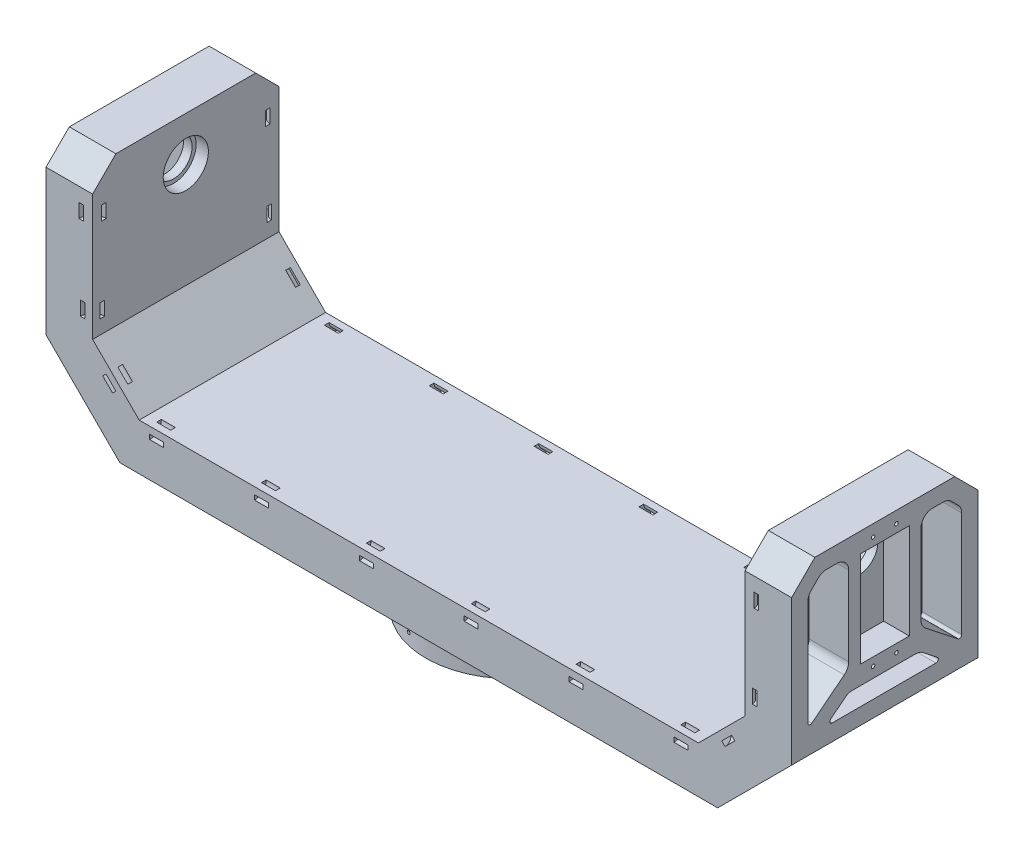
SolidWorks part; units mm, degrees
material "ПК/АБС"
ref_plane "Спереди" through (0, 0, 0) normal (0, 0, 1) x (1, 0, 0)
ref_plane "Сверху" through (0, 0, 0) normal (0, 1, 0) x (1, 0, 0)
ref_plane "Справа" through (0, 0, 0) normal (1, 0, 0) x (0, 0, -1)
sketch "Эскиз1" plane through (0, 0, 0) normal (0, 0, 1) x (1, 0, 0)
  line L0 (0, 0) -> (120, 0)
  line L1 (120, 0) -> (140, 20)
  line L2 (140, 20) -> (140, 84)
  line L3 (140, 84) -> (160, 84)
  line L4 (160, 84) -> (160, 11.7157)
  line L5 (160, 11.7157) -> (128.2843, -20)
  line L6 (128.2843, -20) -> (0, -20)
  line L7 (84.5164, 65) -> (381.3693, 65) construction
  line L8 (0, -20) -> (0, 0)
  dimension "D1" = 65
  dimension "D2" = 20
  dimension "D3" = 20
  dimension "D4" = 20
  dimension "D5" = 140
  dimension "D6" = 19
  dimension "D7" = 120
extrude "Бобышка-Вытянуть1" add sketch "Эскиз1" along normal blind 40 and the other way blind 40
mirror "Зеркальное отражение1" about plane through (0, 0, 0) normal (1, 0, 0) of "Бобышка-Вытянуть1"
chamfer "Фаска1" distance 10 angle 45 4 edges at (150, 84, 40) (150, 84, -40) (-150, 84, -40) (-150, 84, 40)
sketch "Эскиз2" plane through (0, 0, 0) normal (0, 0, 1) x (1, 0, 0)
  line L0 (49.8547, 65) -> (209.3236, 65) construction
  line L1 (120, 0) -> (-120, 0) construction
  line L2 (140, 74.7) -> (145.2775, 74.7)
  line L3 (140, 74) -> (140, 20) construction
  line L4 (145.2775, 74.7) -> (145.2775, 73)
  line L5 (145.2775, 73) -> (160, 73)
  line L6 (160, 11.7157) -> (160, 74) construction
  line L7 (160, 73) -> (160, 65)
  line L8 (160, 65) -> (140, 65)
  line L9 (140, 65) -> (140, 74.7)
  dimension "D1" = 65
  dimension "D2" = 9.7
  dimension "D3" = 8
revolve "Вырез-Повернуть1" cut sketch "Эскиз2" angle 360 about L0
mirror "Зеркальное отражение2" about plane through (0, 0, 0) normal (1, 0, 0) of "Вырез-Повернуть1"
sketch "Эскиз3" plane through (-160, 0, 0) normal (-1, 0, 0) x (0, 0, 1)
  line L0 (-5, 79) -> (-5, 31) construction
  line L1 (-5, 31) -> (5, 31) construction
  line L2 (5, 31) -> (5, 79) construction
  line L3 (5, 79) -> (-5, 79) construction
  line L4 (0, 65) -> (-11.5647, 65) construction
  line L5 (0, 65) -> (0, 85.8977) construction
  circle A0 centre (-5, 79) radius 0.75
  circle A1 centre (5, 79) radius 0.75
  circle A2 centre (-5, 31) radius 0.75
  circle A3 centre (5, 31) radius 0.75
  dimension "D1" = 14
  dimension "D2" = 34
  dimension "D3" = 5
  dimension "D4" = 5
extrude "Вырез-Вытянуть1" cut sketch "Эскиз3" against normal blind 10
sketch "Эскиз4" plane through (-160, 0, 0) normal (-1, 0, 0) x (0, 0, 1)
  line L0 (10.5, 75.5) -> (-10.5, 75.5)
  line L2 (-10.5, 75.5) -> (-10.5, 34.5)
  line L3 (10.5, 34.5) -> (-10.5, 34.5)
  line L5 (0, 65) -> (0, 45.2847) construction
  line L6 (10.5, 75.5) -> (10.5, 34.5)
  dimension "D1" = 10.5
  dimension "D2" = 10.5
  dimension "D3" = 21
  dimension "D4" = 30.5
extrude "Вырез-Вытянуть2" cut sketch "Эскиз4" against normal blind 11
sketch "Эскиз7" plane through (0, -20, 0) normal (0, -1, 0) x (1, 0, 0)
  line L8 (-30, 10.5) -> (10, 10.5)
  line L10 (-30, -10.5) -> (10, -10.5)
  line L12 (-30.5, -10) -> (-30.5, 10)
  line L13 (10.5, -10) -> (10.5, 10)
  line L16 (120.2843, -32) -> (120.2843, 32)
  line L17 (120.2843, 32) -> (-120.2843, 32)
  line L18 (-120.2843, 32) -> (-120.2843, -32)
  line L19 (-120.2843, -32) -> (120.2843, -32)
  line L20 (120.2843, -32) -> (120.2843, 32)
  line L21 (120.2843, 32) -> (-120.2843, 32)
  line L22 (-120.2843, 32) -> (-120.2843, -32)
  line L23 (-120.2843, -32) -> (120.2843, -32)
  circle A0 centre (0, 0) radius 40 construction
  arc A9 (10, 10.5) -> (10.5, 10) centre (10, 10) cw
  arc A10 (10.5, -10) -> (10, -10.5) centre (10, -10) cw
  arc A11 (-30, -10.5) -> (-30.5, -10) centre (-30, -10) cw
  arc A12 (-30.5, 10) -> (-30, 10.5) centre (-30, 10) cw
  dimension "D1" = 8
  dimension "D4" = 0.5
sketch "Эскиз8" plane through (0, -20, 0) normal (0, -1, 0) x (1, 0, 0)
  circle A0 centre (0, 0) radius 37
  circle A1 centre (0, 0) radius 33
  dimension "D1" = 66
  dimension "D2" = 74
extrude "Бобышка-Вытянуть2" add sketch "Эскиз8" along normal blind 10
extrude "Вырез-Вытянуть4" cut sketch "Эскиз7" against normal blind 18.5 contours A12 L12 A11 L10 A10 L13 A9 L8 region at (-10, -20, 0)
sketch "Эскиз9" plane through (0, -20, 0) normal (0, -1, 0) x (1, 0, 0)
  line L0 (-31.5, 10) -> (-31.5, -10)
  line L1 (11.5, 10) -> (11.5, -10)
  line L2 (-38.5, 10) -> (-38.5, -10)
  line L3 (18.5, 10) -> (18.5, -10)
  line L4 (-38.5, 10) -> (-31.5, 10)
  line L5 (-38.5, -10) -> (-31.5, -10)
  line L6 (11.5, 10) -> (18.5, 10)
  line L7 (18.5, -10) -> (11.5, -10)
  dimension "D1" = 7
  dimension "D2" = 7
extrude "Бобышка-Вытянуть3" add sketch "Эскиз9" along normal blind 6
sketch "Эскиз10" plane through (0, -26, 0) normal (0, -1, 0) x (1, 0, 0)
  line L0 (-38.5, 10) -> (-30.5, 10)
  line L1 (-35.623, 10) -> (-38.5, 10) construction
  line L2 (-30.5, 10) -> (-30.5, -10)
  line L3 (-30.5, -10) -> (-38.5, -10)
  line L4 (-38.5, -10) -> (-38.5, 10)
  dimension "D1" = 8
extrude "Вырез-Вытянуть5" cut sketch "Эскиз10" along normal blind 10.5
ref_plane "Плоскость1" through (40, 0, 0) normal (1, 0, 0) x (0, 0, -1)
sketch "Эскиз11" plane through (40, 0, 0) normal (1, 0, 0) x (0, 0, -1)
  line L0 (0, 27.9927) -> (0, -39.0549) construction
  line L1 (-37, -25) -> (45.8184, -25) construction
  line L2 (-37, -20) -> (-37, -30) construction
  circle A0 centre (0, -25) radius 0.75
extrude "Вырез-Вытянуть6" cut sketch "Эскиз11" against normal blind 10.5
pattern_circular "Круговой массив1" count 7 over 360 about axis through (0, -30, 0) along (0, 1, 0) of "Вырез-Вытянуть6"
mirror "Зеркальное отражение3" about plane through (0, 0, 0) normal (1, 0, 0) of "Вырез-Вытянуть2", "Вырез-Вытянуть1"
sketch "Эскиз12" plane through (-160, 0, 0) normal (-1, 0, 0) x (0, 0, 1)
  line L0 (-31.5355, 72.565) -> (-28.565, 75.5355)
  line L1 (-25.0294, 77) -> (-20.5, 77)
  line L2 (-15.5, 72) -> (-15.5, 37.9357)
  line L3 (22.6012, 18.7157) -> (-21.9677, 18.7157)
  line L4 (-33, 23.763) -> (-33, 69.0294)
  line L5 (-40, 11.7157) -> (-40, 74) construction
  line L6 (-30, 84) -> (-40, 74) construction
  line L7 (-30, 84) -> (30, 84) construction
  line L8 (-10.5, 75.5) -> (-10.5, 34.5) construction
  line L9 (-40, 11.7157) -> (40, 11.7157) construction
  line L10 (0, 14.9515) -> (0, 96.0937) construction
  line L11 (33, 23.763) -> (33, 69.0294)
  line L13 (15.5, 72) -> (15.5, 37.9357)
  line L14 (25.0294, 77) -> (20.5, 77)
  line L15 (31.5355, 72.565) -> (28.565, 75.5355)
  line L18 (-22.5873, 20.5007) -> (-16.3487, 25.4248)
  line L19 (16.9822, 25.4248) -> (23.2207, 20.5007)
  line L20 (-31.3804, 22.978) -> (-17.4022, 34.011)
  line L21 (17.4022, 34.011) -> (31.3804, 22.978)
  line L22 (-13.2509, 26.5) -> (13.8844, 26.5)
  line L23 (-10.5, 34.5) -> (10.5, 34.5) construction
  arc A0 (-33, 69.0294) -> (-31.5355, 72.565) centre (-28, 69.0294) cw
  arc A1 (-28.565, 75.5355) -> (-25.0294, 77) centre (-25.0294, 72) cw
  arc A2 (-15.5, 72) -> (-20.5, 77) centre (-20.5, 72) ccw
  arc A7 (15.5, 72) -> (20.5, 77) centre (20.5, 72) cw
  arc A8 (28.565, 75.5355) -> (25.0294, 77) centre (25.0294, 72) ccw
  arc A9 (33, 69.0294) -> (31.5355, 72.565) centre (28, 69.0294) ccw
  arc A10 (23.2207, 20.5007) -> (22.6012, 18.7157) centre (22.6012, 19.7157) cw
  arc A11 (-22.5873, 20.5007) -> (-21.9677, 18.7157) centre (-21.9677, 19.7157) ccw
  arc A12 (16.9822, 25.4248) -> (13.8844, 26.5) centre (13.8844, 21.5) ccw
  arc A13 (-13.2509, 26.5) -> (-16.3487, 25.4248) centre (-13.2509, 21.5) ccw
  arc A14 (33, 23.763) -> (31.3804, 22.978) centre (32, 23.763) cw
  arc A15 (-31.3804, 22.978) -> (-33, 23.763) centre (-32, 23.763) cw
  arc A16 (17.4022, 34.011) -> (15.5, 37.9357) centre (20.5, 37.9357) cw
  arc A17 (-15.5, 37.9357) -> (-17.4022, 34.011) centre (-20.5, 37.9357) cw
  point P53 (-37.8315, 8.9684)
  point P54 (-8.3315, 32.2527)
  point P55 (8.3315, 32.2527)
  point P56 (37.8315, 8.9684)
  point P57 (-42.1685, 14.4631)
  point P58 (-12.6685, 37.7473)
  point P59 (12.6685, 37.7473)
  point P60 (42.1685, 14.4631)
  dimension "D6" = 5
  dimension "D7" = 1
  dimension "D8" = 1
  dimension "D10" = 5
  dimension "D11" = 1
  dimension "D12" = 1
  dimension "D13" = 5
  dimension "D1" = 7
  dimension "D2" = 7
  dimension "D3" = 7
  dimension "D4" = 5
  dimension "D5" = 7
  dimension "D9" = 8
extrude "Вырез-Вытянуть7" cut sketch "Эскиз12" against normal blind 17
sketch "Эскиз13" plane through (-74.1421, -74.1421, 0) normal (-0.7071, -0.7071, 0) x (0, 0, 1)
  line L6 (-16.5294, 114.4214) -> (16.5294, 114.4214)
  line L7 (17.0185, 112.5491) -> (1.4671, 103.8301)
  line L8 (-40, 121.4214) -> (40, 121.4214) construction
  line L10 (1.4671, 94.1598) -> (17.0185, 85.4408)
  line L11 (8.7126, 98.1227) -> (31.511, 85.3406)
  line L12 (-31.511, 112.6493) -> (-8.7126, 99.8672)
  line L13 (31.511, 112.6493) -> (8.7126, 99.8672)
  line L14 (-17.0185, 112.5491) -> (-1.4671, 103.8301)
  line L15 (-16.5294, 83.5685) -> (16.5294, 83.5685)
  line L16 (-1.4671, 94.1598) -> (-17.0185, 85.4408)
  line L17 (-8.7126, 98.1227) -> (-31.511, 85.3406)
  line L18 (-33, 111.7771) -> (-33, 86.2128)
  line L19 (-40, 76.5685) -> (40, 76.5685) construction
  line L22 (33, 111.7771) -> (33, 86.2128)
  line L24 (-40, 76.5685) -> (-40, 121.4214) construction
  line L25 (40, 76.5685) -> (40, 121.4214) construction
  arc A0 (-1.4671, 94.1598) -> (1.4671, 94.1598) centre (0, 91.543) cw
  arc A1 (1.4671, 103.8301) -> (-1.4671, 103.8301) centre (0, 106.4469) cw
  arc A4 (31.511, 85.3406) -> (33, 86.2128) centre (32, 86.2128) ccw
  arc A5 (33, 111.7771) -> (31.511, 112.6493) centre (32, 111.7771) ccw
  arc A6 (-31.511, 112.6493) -> (-33, 111.7771) centre (-32, 111.7771) ccw
  arc A7 (-33, 86.2128) -> (-31.511, 85.3406) centre (-32, 86.2128) ccw
  arc A12 (8.7126, 98.1227) -> (8.7126, 99.8672) centre (9.2017, 98.9949) cw
  arc A13 (-8.7126, 98.1227) -> (-8.7126, 99.8672) centre (-9.2017, 98.9949) ccw
  arc A14 (-16.5294, 83.5685) -> (-17.0185, 85.4408) centre (-16.5294, 84.5685) cw
  arc A15 (16.5294, 83.5685) -> (17.0185, 85.4408) centre (16.5294, 84.5685) ccw
  arc A16 (17.0185, 112.5491) -> (16.5294, 114.4214) centre (16.5294, 113.4214) ccw
  arc A17 (-17.0185, 112.5491) -> (-16.5294, 114.4214) centre (-16.5294, 113.4214) cw
  point P20 (0, 94.9824)
  point P29 (-7.1569, 98.9949)
  dimension "D2" = 3
  dimension "D1" = 1
  dimension "D5" = 1
  dimension "D3" = 7
  dimension "D4" = 7
  dimension "D6" = 7
  dimension "D7" = 7
extrude "Вырез-Вытянуть8" cut sketch "Эскиз13" against normal blind 15
sketch "Эскиз14" plane through (0, -20, 0) normal (0, -1, 0) x (1, 0, 0)
  line L0 (-59.773, 1.6912) -> (-37.4271, 15.7975)
  line L1 (73.5087, -33) -> (107.8127, -33)
  line L2 (-78.2445, 1.6912) -> (-118.2167, 26.9245)
  line L3 (-63.4411, 7.6537) -> (-29.1372, 29.3088)
  line L5 (30.2048, -33) -> (64.5087, -33)
  line L6 (121.2843, -25.2333) -> (121.2843, 25.2333)
  line L7 (107.8127, 33) -> (73.5087, 33)
  line L8 (0, 0) -> (0, -74.0699) construction
  line L9 (-74.5763, 7.6537) -> (-108.8803, 29.3088)
  line L10 (-37.4271, -15.7975) -> (-59.773, -1.6912)
  line L11 (-108.8803, -29.3088) -> (-74.5763, -7.6537)
  line L12 (118.2167, -26.9245) -> (78.2445, -1.6912)
  line L13 (29.1372, -29.3088) -> (63.4411, -7.6537)
  line L14 (108.8803, -29.3088) -> (74.5763, -7.6537)
  line L15 (37.4271, -15.7975) -> (59.773, -1.6912)
  line L16 (74.5763, 7.6537) -> (108.8803, 29.3088)
  line L17 (-29.1372, -29.3088) -> (-63.4411, -7.6537)
  line L18 (-118.2167, -26.9245) -> (-78.2445, -1.6912)
  line L19 (-107.8127, 33) -> (-73.5087, 33)
  line L20 (-121.2843, -25.2333) -> (-121.2843, 25.2333)
  line L21 (-30.2048, -33) -> (-64.5087, -33)
  line L22 (63.4411, 7.6537) -> (29.1372, 29.3088)
  line L23 (78.2445, 1.6912) -> (118.2167, 26.9245)
  line L24 (59.773, 1.6912) -> (37.4271, 15.7975)
  line L25 (-35.623, -10) -> (-38.5, -10)
  line L26 (-38.5, -10) -> (-38.5, 10)
  line L27 (-38.5, 10) -> (-35.623, 10)
  line L28 (66.5087, -9.3449) -> (66.5087, -31)
  line L29 (-71.5087, 31) -> (-71.5087, 9.3449)
  line L30 (-66.5087, 31) -> (-66.5087, 9.3449)
  line L31 (-71.5087, -9.3449) -> (-71.5087, -31)
  line L32 (-66.5087, -9.3449) -> (-66.5087, -31)
  line L33 (71.5087, -9.3449) -> (71.5087, -31)
  line L34 (66.5087, 31) -> (66.5087, 9.3449)
  line L35 (71.5087, 31) -> (71.5087, 9.3449)
  line L36 (-73.5087, -33) -> (-107.8127, -33)
  line L37 (-64.5087, 33) -> (-30.2048, 33)
  line L38 (64.5087, 33) -> (30.2048, 33)
  arc A1 (30.2048, -33) -> (29.1372, -29.3088) centre (30.2048, -31) cw
  arc A2 (34.4949, -13.3829) -> (34.4949, 13.3829) centre (0, 0) ccw
  arc A4 (34.4949, -13.3829) -> (37.4271, -15.7975) centre (36.3595, -14.1063) ccw
  arc A5 (59.773, -1.6912) -> (59.773, 1.6912) centre (58.7054, 0) ccw
  arc A6 (34.4949, 13.3829) -> (37.4271, 15.7975) centre (36.3595, 14.1063) cw
  arc A7 (29.1372, 29.3088) -> (30.2048, 33) centre (30.2048, 31) cw
  arc A9 (107.8127, 33) -> (108.8803, 29.3088) centre (107.8127, 31) cw
  arc A10 (121.2843, 25.2333) -> (118.2167, 26.9245) centre (119.2843, 25.2333) ccw
  arc A11 (78.2445, 1.6912) -> (78.2445, -1.6912) centre (79.3121, 0) ccw
  arc A12 (121.2843, -25.2333) -> (118.2167, -26.9245) centre (119.2843, -25.2333) cw
  arc A13 (108.8803, -29.3088) -> (107.8127, -33) centre (107.8127, -31) cw
  arc A14 (-108.8803, -29.3088) -> (-107.8127, -33) centre (-107.8127, -31) ccw
  arc A15 (-121.2843, -25.2333) -> (-118.2167, -26.9245) centre (-119.2843, -25.2333) ccw
  arc A16 (-78.2445, 1.6912) -> (-78.2445, -1.6912) centre (-79.3121, 0) cw
  arc A17 (-121.2843, 25.2333) -> (-118.2167, 26.9245) centre (-119.2843, 25.2333) cw
  arc A18 (-107.8127, 33) -> (-108.8803, 29.3088) centre (-107.8127, 31) ccw
  arc A20 (-29.1372, 29.3088) -> (-30.2048, 33) centre (-30.2048, 31) ccw
  arc A21 (-34.4949, 13.3829) -> (-37.4271, 15.7975) centre (-36.3595, 14.1063) ccw
  arc A22 (-59.773, -1.6912) -> (-59.773, 1.6912) centre (-58.7054, 0) cw
  arc A23 (-34.4949, -13.3829) -> (-37.4271, -15.7975) centre (-36.3595, -14.1063) cw
  arc A25 (-34.4949, -13.3829) -> (-35.623, -10) centre (0, 0) cw
  arc A26 (-30.2048, -33) -> (-29.1372, -29.3088) centre (-30.2048, -31) ccw
  arc A27 (-35.623, 10) -> (-34.4949, 13.3829) centre (0, 0) cw
  arc A28 (74.5763, 7.6537) -> (71.5087, 9.3449) centre (73.5087, 9.3449) cw
  arc A29 (71.5087, 31) -> (73.5087, 33) centre (73.5087, 31) cw
  arc A30 (66.5087, 31) -> (64.5087, 33) centre (64.5087, 31) ccw
  arc A31 (63.4411, 7.6537) -> (66.5087, 9.3449) centre (64.5087, 9.3449) ccw
  arc A32 (71.5087, -31) -> (73.5087, -33) centre (73.5087, -31) ccw
  arc A33 (74.5763, -7.6537) -> (71.5087, -9.3449) centre (73.5087, -9.3449) ccw
  arc A34 (63.4411, -7.6537) -> (66.5087, -9.3449) centre (64.5087, -9.3449) cw
  arc A35 (66.5087, -31) -> (64.5087, -33) centre (64.5087, -31) cw
  arc A36 (-64.5087, -33) -> (-66.5087, -31) centre (-64.5087, -31) cw
  arc A37 (-71.5087, -31) -> (-73.5087, -33) centre (-73.5087, -31) cw
  arc A38 (-74.5763, -7.6537) -> (-71.5087, -9.3449) centre (-73.5087, -9.3449) cw
  arc A39 (-63.4411, -7.6537) -> (-66.5087, -9.3449) centre (-64.5087, -9.3449) ccw
  arc A40 (-74.5763, 7.6537) -> (-71.5087, 9.3449) centre (-73.5087, 9.3449) ccw
  arc A41 (-66.5087, 9.3449) -> (-63.4411, 7.6537) centre (-64.5087, 9.3449) ccw
  arc A42 (-66.5087, 31) -> (-64.5087, 33) centre (-64.5087, 31) cw
  arc A43 (-71.5087, 31) -> (-73.5087, 33) centre (-73.5087, 31) ccw
  point P5 (0, -33)
  point P11 (121.2843, -33)
  point P12 (121.2843, 33)
  point P13 (0, 33)
  point P15 (123.1526, -30.0404)
  point P19 (18.6015, 35.9596)
  point P20 (18.6015, -35.9596)
  point P21 (123.1526, 30.0404)
  point P22 (119.4159, -35.9596)
  point P23 (14.8649, 30.0404)
  point P24 (14.8649, -30.0404)
  point P25 (119.4159, 35.9596)
  point P39 (71.5087, 5.7172)
  point P45 (62.4521, 0)
  point P52 (69.0087, 4.139)
  point P59 (75.5654, 0)
  point P87 (66.5087, 33)
  point P92 (-75.5654, 0)
  point P93 (-69.0087, 4.139)
  point P94 (-62.4521, 0)
  point P105 (-71.5087, 45.7919)
  point P106 (-71.5087, -37.1634)
  point P107 (-66.5087, 45.7919)
  point P108 (-66.5087, -37.1634)
  point P114 (66.5087, 5.7172)
  point P118 (71.5087, -33)
  point P125 (71.5087, -5.7172)
  point P128 (66.5087, -5.7172)
  point P135 (-71.5087, -33)
  point P138 (-71.5087, -5.7172)
  point P141 (-66.5087, -5.7172)
  point P144 (-71.5087, 5.7172)
  point P147 (-66.5087, 5.7172)
  point P150 (-66.5087, 33)
  dimension "D2" = 2
  dimension "D1" = 2
extrude "Вырез-Вытянуть9" cut sketch "Эскиз14" against normal blind 17
sketch "Эскиз15" plane through (0, -20, 0) normal (0, -1, 0) x (1, 0, 0)
  line L0 (-28.5263, 15.5) -> (10.5, 15.5)
  line L1 (-28.5263, -15.5) -> (10.5, -15.5)
  line L2 (-30, -10.5) -> (10, -10.5) construction
  line L3 (-30, 10.5) -> (10, 10.5) construction
  line L4 (-21.7198, 22.5) -> (21.7198, 22.5)
  line L5 (-21.7198, -22.5) -> (21.7198, -22.5)
  line L6 (18.5, 10) -> (18.5, 14.5)
  line L8 (11.5, 10) -> (11.5, 14.5)
  line L9 (19.5, 15.5) -> (28.5263, 15.5)
  line L10 (18.5, 10) -> (18.5, -14.5)
  line L12 (11.5, 10) -> (11.5, -14.5)
  line L13 (19.5, -15.5) -> (28.5263, -15.5)
  line L19 (-31.5, 9.8362) -> (-31.5, -9.8362)
  arc A0 (-22.3986, -24.2344) -> (22.3986, -24.2344) centre (0, 0) ccw
  arc A1 (29.4178, -14.9531) -> (29.4178, 14.9531) centre (0, 0) ccw
  arc A2 (22.3986, 24.2344) -> (-22.3986, 24.2344) centre (0, 0) ccw
  arc A3 (-29.4178, 14.9531) -> (-31.5, 9.8362) centre (0, 0) ccw
  arc A4 (-22.3986, -24.2344) -> (-21.7198, -22.5) centre (-21.7198, -23.5) cw
  arc A5 (22.3986, -24.2344) -> (21.7198, -22.5) centre (21.7198, -23.5) ccw
  arc A6 (22.3986, 24.2344) -> (21.7198, 22.5) centre (21.7198, 23.5) cw
  arc A7 (-22.3986, 24.2344) -> (-21.7198, 22.5) centre (-21.7198, 23.5) ccw
  arc A8 (-28.5263, -15.5) -> (-29.4178, -14.9531) centre (-28.5263, -14.5) cw
  arc A9 (-29.4178, 14.9531) -> (-28.5263, 15.5) centre (-28.5263, 14.5) cw
  arc A10 (18.5, 14.5) -> (19.5, 15.5) centre (19.5, 14.5) cw
  arc A11 (10.5, 15.5) -> (11.5, 14.5) centre (10.5, 14.5) cw
  arc A12 (11.5, -14.5) -> (10.5, -15.5) centre (10.5, -14.5) cw
  arc A13 (18.5, -14.5) -> (19.5, -15.5) centre (19.5, -14.5) ccw
  arc A14 (28.5263, -15.5) -> (29.4178, -14.9531) centre (28.5263, -14.5) ccw
  arc A15 (29.4178, 14.9531) -> (28.5263, 15.5) centre (28.5263, 14.5) ccw
  arc A16 (-31.5, -9.8362) -> (-29.4178, -14.9531) centre (0, 0) ccw
  point P32 (24.1402, 22.5)
  point P35 (-24.1402, 22.5)
  point P40 (-29.1333, 15.5)
  point P43 (18.5, 15.5)
  point P50 (18.5, -15.5)
  point P53 (29.1333, -15.5)
  point P56 (29.1333, 15.5)
  dimension "D5" = 1
  dimension "D6" = 1
  dimension "D7" = 7
  dimension "D1" = 5
  dimension "D2" = 5
  dimension "D3" = 7
  dimension "D4" = 7
extrude "Вырез-Вытянуть10" cut sketch "Эскиз15" against normal blind 17
sketch "Эскиз16" plane through (10.5, 0, 0) normal (-1, 0, 0) x (0, 0, 1)
  line L0 (0, 0) -> (0, -26) construction
  line L1 (10, 0) -> (-10, 0) construction
  line L2 (10, -26) -> (-10, -26) construction
  line L4 (-3, -12) -> (3, -12)
  line L5 (-4, -11) -> (-4, -6)
  line L6 (-3, -5) -> (3, -5)
  line L7 (4, -11) -> (4, -6)
  arc A0 (-4, -11) -> (-3, -12) centre (-3, -11) ccw
  arc A1 (3, -12) -> (4, -11) centre (3, -11) ccw
  arc A2 (4, -6) -> (3, -5) centre (3, -6) ccw
  arc A3 (-3, -5) -> (-4, -6) centre (-3, -6) ccw
  point P12 (-4, -12)
  point P19 (-4, -5)
  dimension "D5" = 1
  dimension "D1" = 14
  dimension "D2" = 7
  dimension "D3" = 4
  dimension "D4" = 4
extrude "Вырез-Вытянуть11" cut sketch "Эскиз16" against normal blind 37
mirror "Зеркальное отражение4" about plane through (0, 0, 0) normal (1, 0, 0) of "Вырез-Вытянуть8", "Вырез-Вытянуть7"
sketch "Эскиз17" plane through (0, -26, 0) normal (0, -1, 0) x (1, 0, 0)
  line L0 (-38.5, 0) -> (18.5, 0) construction
  line L1 (-38.5, 10) -> (-38.5, -10) construction
  line L2 (18.5, -10) -> (18.5, 10) construction
  line L3 (-34, 13.7966) -> (-34, -13.661) construction
  line L4 (14, 13.7966) -> (14, -13.661) construction
  line L5 (-38.5, -5) -> (18.5, -5) construction
  line L6 (-38.5, 5) -> (18.5, 5) construction
  line L7 (-10, 5) -> (-10, 13.7966) construction
  circle A0 centre (-34, 5) radius 0.75
  circle A1 centre (14, 5) radius 0.75
  circle A2 centre (14, -5) radius 0.75
  circle A3 centre (-34, -5) radius 0.75
  dimension "D1" = 48
  dimension "D4" = 24
  dimension "D2" = 5
  dimension "D3" = 5
extrude "Вырез-Вытянуть13" cut sketch "Эскиз17" against normal blind 10
sketch "Эскиз18" plane through (0, 0, 40) normal (0, 0, 1) x (1, 0, 0)
  line L0 (0, 0) -> (0, -24.1802) construction
  line L1 (19.5, -3) -> (25.5, -3)
  line L2 (19.5, -3) -> (19.5, -5)
  line L3 (19.5, -5) -> (25.5, -5)
  line L4 (25.5, -3) -> (25.5, -5)
  line L5 (64.5, -3) -> (70.5, -3)
  line L6 (64.5, -3) -> (64.5, -5)
  line L7 (64.5, -5) -> (70.5, -5)
  line L8 (70.5, -3) -> (70.5, -5)
  line L9 (120, 0) -> (-120, 0) construction
  line L10 (109.5, -3) -> (115.5, -3)
  line L11 (109.5, -3) -> (109.5, -5)
  line L12 (109.5, -5) -> (115.5, -5)
  line L13 (115.5, -3) -> (115.5, -5)
  line L14 (-115.5, -3) -> (-115.5, -5)
  line L15 (-109.5, -5) -> (-115.5, -5)
  line L16 (-109.5, -3) -> (-109.5, -5)
  line L17 (-109.5, -3) -> (-115.5, -3)
  line L18 (-70.5, -3) -> (-70.5, -5)
  line L19 (-64.5, -5) -> (-70.5, -5)
  line L20 (-64.5, -3) -> (-64.5, -5)
  line L21 (-64.5, -3) -> (-70.5, -3)
  line L22 (-25.5, -3) -> (-25.5, -5)
  line L23 (-19.5, -5) -> (-25.5, -5)
  line L24 (-19.5, -3) -> (-19.5, -5)
  line L25 (-19.5, -3) -> (-25.5, -3)
  dimension "D1" = 2
  dimension "D2" = 6
  dimension "D3" = 19.5
  dimension "D4" = 3
  dimension "D6" = 45
  dimension "D7" = 45
  dimension "D8" = 45
  dimension "D5" = 2
sketch "Эскиз19" plane through (0, 0, 40) normal (0, 0, 1) x (1, 0, 0)
  line L0 (130, 10) -> (136.5274, 3.4726) construction
  line L1 (130, 5.7574) -> (134.2426, 10)
  line L2 (134.2426, 10) -> (135.6569, 8.5858)
  line L3 (135.6569, 8.5858) -> (131.4142, 4.3431)
  line L4 (131.4142, 4.3431) -> (130, 5.7574)
  point P4 (130.7071, 5.0503)
  dimension "D1" = 3
  dimension "D2" = 3
  dimension "D3" = 2
sketch "Эскиз20" plane through (0, 0, 40) normal (0, 0, 1) x (1, 0, 0)
  line L1 (143.1831, 32) -> (145.1831, 32)
  line L2 (143.1831, 32) -> (143.1831, 26)
  line L3 (143.1831, 26) -> (145.1831, 26)
  line L4 (145.1831, 32) -> (145.1831, 26)
  line L5 (143.8572, 68) -> (145.8572, 68)
  line L6 (143.8572, 68) -> (143.8572, 62)
  line L7 (143.8572, 62) -> (145.8572, 62)
  line L8 (145.8572, 68) -> (145.8572, 62)
  point P8 (144.8572, 68)
  dimension "D1" = 6
  dimension "D2" = 36
  dimension "D3" = 6
  dimension "D4" = 6
  dimension "D5" = 2
  dimension "D6" = 2
revolve "Вырез-Повернуть2" cut sketch "Эскиз18" angle 360 about axis through (0, 0, 40) along (-1, 0, 0)
revolve "Вырез-Повернуть3" cut sketch "Эскиз19" angle 360 about axis through (120, 0, 40) along (-0.7071, -0.7071, 0)
revolve "Вырез-Повернуть4" cut sketch "Эскиз20" angle 360 about axis through (140, 20, 40) along (0, -1, 0)
mirror "Зеркальное отражение5" about plane through (0, 0, 0) normal (1, 0, 0) of "Вырез-Повернуть3"
mirror "Зеркальное отражение6" about plane through (0, 0, 0) normal (1, 0, 0) of "Вырез-Повернуть4"
mirror "Зеркальное отражение7" about plane through (0, 0, 0) normal (0, 0, 1) of "Зеркальное отражение6", "Зеркальное отражение5", "Вырез-Повернуть4", "Вырез-Повернуть3", "Вырез-Повернуть2"
